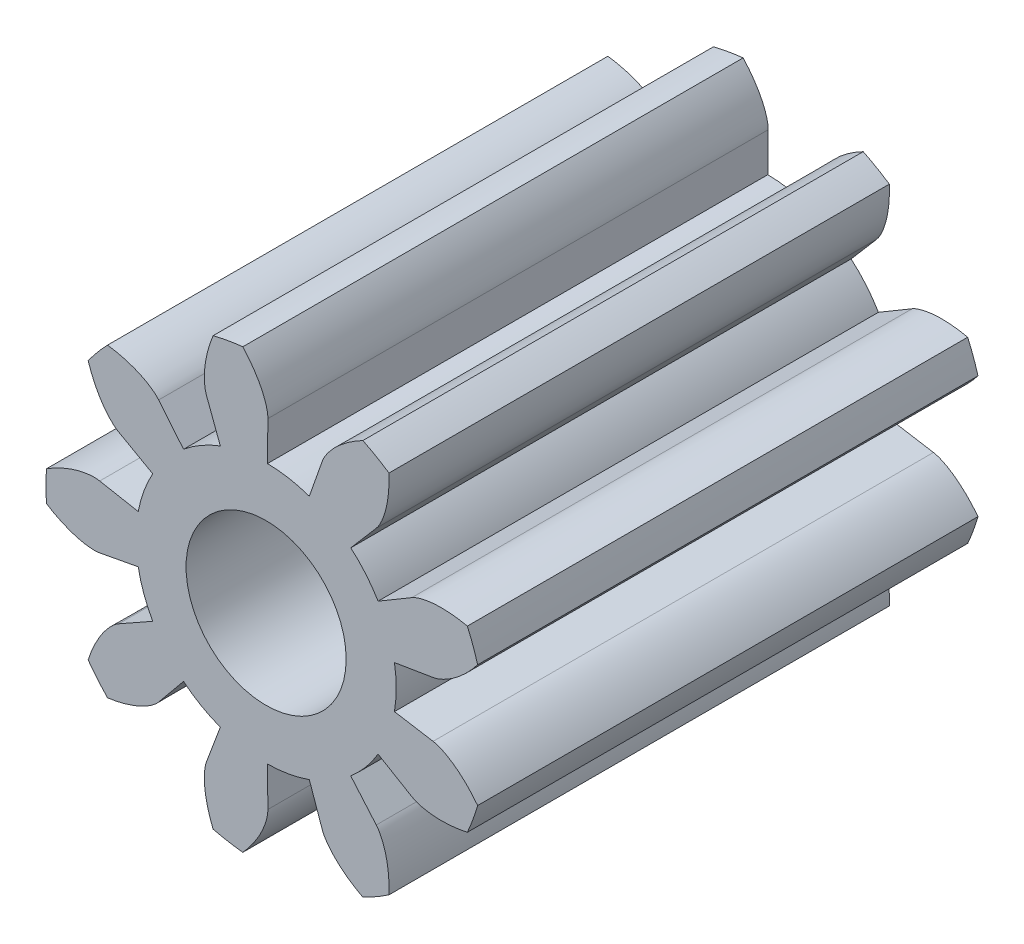
SolidWorks part; units mm, degrees
ref_plane "前视基准面" through (0, 0, 0) normal (0, 0, 1) x (1, 0, 0)
ref_plane "上视基准面" through (0, 0, 0) normal (0, 1, 0) x (1, 0, 0)
ref_plane "右视基准面" through (0, 0, 0) normal (1, 0, 0) x (0, 0, -1)
other "Configuration Table"
sketch "草图1" plane through (0, 0, 0) normal (0, 0, 1) x (1, 0, 0)
  line L0 (0, 0) -> (0.9, 0) construction
  line L1 (0, 0) -> (0.8863, 0.1563) construction
  line L2 (0, 0) -> (0.8344, 0.1381)
  line L3 (0.8863, 0.1563) -> (0.8863, -0.1563) construction
  line L4 (0, 0) -> (0.8344, -0.1381)
  circle A0 centre (0, 0) radius 1.1
  circle A1 centre (0, 0) radius 0.9 construction
  circle A2 centre (0, 0) radius 0.65
  circle A3 centre (0, 0) radius 0.8457 construction
  circle A4 centre (0, 0) radius 0.4
  spline S0 degree 4 poles (0.8344, 0.1381) (0.8407, 0.1391) (0.8583, 0.1434) (0.8902, 0.1567) (0.9385, 0.1852) (0.9947, 0.2314) (1.0578, 0.3003) (1.1187, 0.3914) (1.1706, 0.5) (1.2099, 0.6235) (1.2335, 0.7509) (1.2426, 0.8802) (1.238, 1.016) (1.2147, 1.1827) (1.1617, 1.3766) (1.0676, 1.5905) (0.9281, 1.8092) (0.7581, 2.0054) (0.5641, 2.1769) (0.3484, 2.322) (0.1192, 2.4402) (-0.1262, 2.5304) (-0.3732, 2.5938) (-0.6374, 2.6288) (-0.8395, 2.6375) (-1.0646, 2.6268) (-1.2145, 2.6094) (-1.3852, 2.5832) (-1.4515, 2.5634) (-1.518, 2.549) knots 0 0 0 0 0 0.005604 0.015718 0.02996 0.048734 0.068727 0.096889 0.125051 0.153212 0.181374 0.209535 0.237696 0.271429 0.327752 0.384075 0.440398 0.496721 0.553044 0.609367 0.66569 0.722013 0.778336 0.834659 0.890982 0.909091 0.954545 1 1 1 1 1 construction
  spline S1 degree 4 poles (0.8344, 0.1381) (0.8407, 0.1391) (0.8583, 0.1434) (0.8902, 0.1567) (0.9385, 0.1852) (0.9947, 0.2314) (1.0578, 0.3003) (1.1187, 0.3914) (1.1706, 0.5) (1.2099, 0.6235) (1.2335, 0.7509) (1.2426, 0.8802) (1.238, 1.016) (1.2147, 1.1827) (1.1617, 1.3766) (1.0676, 1.5905) (0.9281, 1.8092) (0.7581, 2.0054) (0.5641, 2.1769) (0.3484, 2.322) (0.1192, 2.4402) (-0.1262, 2.5304) (-0.3732, 2.5938) (-0.6374, 2.6288) (-0.8395, 2.6375) (-1.0065, 2.6296) (-1.0845, 2.623) (-1.1033, 2.6212) knots 0 0 0 0 0 0.005604 0.015718 0.02996 0.048734 0.068727 0.096889 0.125051 0.153212 0.181374 0.209535 0.237696 0.271429 0.327752 0.384075 0.440398 0.496721 0.553044 0.609367 0.66569 0.722013 0.778336 0.834659 0.890982 0.909091 0.909091 0.909091 0.909091 0.909091
  spline S2 degree 4 poles (0.8344, -0.1381) (0.8407, -0.1391) (0.8583, -0.1434) (0.8902, -0.1567) (0.9385, -0.1852) (0.9947, -0.2314) (1.0578, -0.3003) (1.1187, -0.3914) (1.1706, -0.5) (1.2099, -0.6235) (1.2335, -0.7509) (1.2426, -0.8802) (1.238, -1.016) (1.2147, -1.1827) (1.1617, -1.3766) (1.0676, -1.5905) (0.9281, -1.8092) (0.7581, -2.0054) (0.5641, -2.1769) (0.3484, -2.322) (0.1192, -2.4402) (-0.1262, -2.5304) (-0.3732, -2.5938) (-0.6374, -2.6288) (-0.8395, -2.6375) (-1.0646, -2.6268) (-1.2145, -2.6094) (-1.3852, -2.5832) (-1.4515, -2.5634) (-1.518, -2.549) knots 0 0 0 0 0 0.005604 0.015718 0.02996 0.048734 0.068727 0.096889 0.125051 0.153212 0.181374 0.209535 0.237696 0.271429 0.327752 0.384075 0.440398 0.496721 0.553044 0.609367 0.66569 0.722013 0.778336 0.834659 0.890982 0.909091 0.954545 1 1 1 1 1 construction
  spline S3 degree 4 poles (0.8344, -0.1381) (0.8407, -0.1391) (0.8583, -0.1434) (0.8902, -0.1567) (0.9385, -0.1852) (0.9947, -0.2314) (1.0578, -0.3003) (1.1187, -0.3914) (1.1706, -0.5) (1.2099, -0.6235) (1.2335, -0.7509) (1.2426, -0.8802) (1.238, -1.016) (1.2147, -1.1827) (1.1617, -1.3766) (1.0676, -1.5905) (0.9281, -1.8092) (0.7581, -2.0054) (0.5641, -2.1769) (0.3484, -2.322) (0.1192, -2.4402) (-0.1262, -2.5304) (-0.3732, -2.5938) (-0.6374, -2.6288) (-0.8395, -2.6375) (-1.0065, -2.6296) (-1.0845, -2.623) (-1.1033, -2.6212) knots 0 0 0 0 0 0.005604 0.015718 0.02996 0.048734 0.068727 0.096889 0.125051 0.153212 0.181374 0.209535 0.237696 0.271429 0.327752 0.384075 0.440398 0.496721 0.553044 0.609367 0.66569 0.722013 0.778336 0.834659 0.890982 0.909091 0.909091 0.909091 0.909091 0.909091
  point P15 (0.8863, 0)
  dimension "齿顶圆直径" = 2.2
  dimension "分度圆直径" = 1.8
  dimension "齿根圆直径" = 1.3
  dimension "基圆直径" = 1.6914
  dimension "内孔直径" = 0.8
  dimension "渐近线镜像线夹角" = 10
extrude "凸台-拉伸1" add sketch "草图1" along normal blind 2.5 contours A0 | A4
extrude "切除-拉伸1" cut sketch "草图1<3>" along normal through all contours A2 S3 A0 S1 region at (0.9092, 0, 0)
sketch "草图1<3>" plane through (0, 0, 0) normal (0, 0, 1) x (1, 0, 0) same geometry as "草图1"
pattern_circular "阵列(圆周)1" count 9 every 40 about axis through (0, 0, 2.5) along (0, 0, 1) of "切除-拉伸1"
equation "\"m\"= 0.2'模数"
equation "\"z\"= 9'齿数"
equation "\"a\"= 20度'压力角"
equation "\"d\"= \"m\" * \"z\"'分度圆直径"
equation "\"da\"= ( \"z\" + 2 ) * \"m\"'齿顶圆直径"
equation "\"df\"= ( \"z\" - 2.5 ) * \"m\"'齿根圆直径"
equation "\"s\"= 0.5 * PI * \"m\"'分度圆齿厚"
equation "\"r\"= 0.38 * \"m\"'齿根圆角"
equation "\"B\"= 0.3 * \"d\"'齿厚"
equation "\"db\"= \"m\" * \"z\" * cos ( \"a\" )'基圆直径"
equation "\"rb\"= \"db\" / 2'基圆半径"
equation "\"齿顶圆直径@草图1\"= \"da\""
equation "\"分度圆直径@草图1\"= \"d\""
equation "\"齿根圆直径@草图1\"= \"df\""
equation "\"基圆直径@草图1\"= \"db\""
equation "\"渐近线镜像线夹角@草图1\"= 360 / 4 / \"z\""
equation "\"h\"= 2.5'齿轮厚度"
equation "\"ir\"= 0.8'内孔直径"
equation "\"内孔直径@草图1\"= \"ir\""
equation "\"齿轮厚@凸台-拉伸1\"= \"h\""
equation "\"齿轮夹角@阵列(圆周)1\"= 360 / \"z\""
equation "\"齿数@阵列(圆周)1\"= \"z\""
